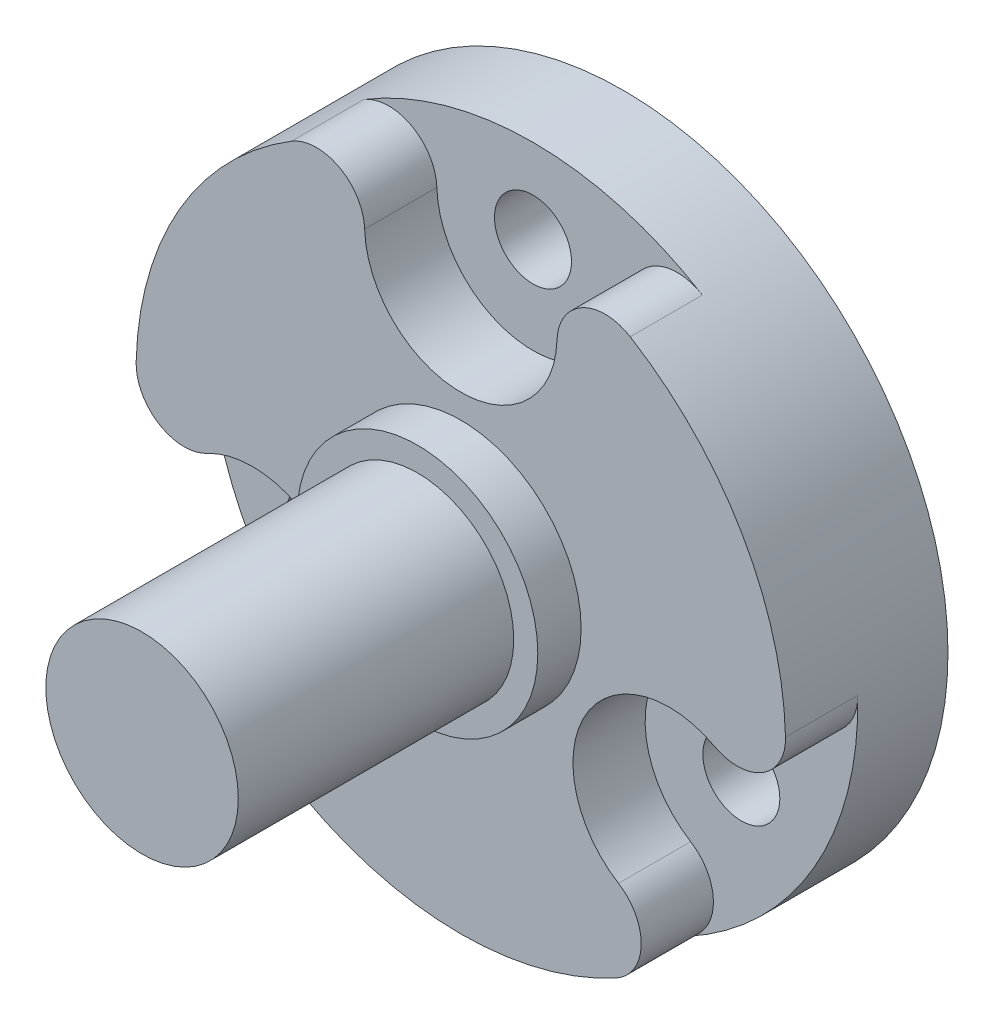
SolidWorks part; units mm, degrees
material "5052-H34"
ref_plane "正面" through (0, 0, 0) normal (0, 0, 1) x (1, 0, 0)
ref_plane "平面" through (0, 0, 0) normal (0, 1, 0) x (1, 0, 0)
ref_plane "右側面" through (0, 0, 0) normal (1, 0, 0) x (0, 0, -1)
sketch "ｽｹｯﾁ1" plane through (0, 0, 0) normal (0, 0, 1) x (1, 0, 0)
  circle A0 centre (0, 0) radius 13.5
  dimension "D1" = 27
extrude "ﾎﾞｽ - 押し出し1" add sketch "ｽｹｯﾁ1" along normal blind 20
sketch "ｽｹｯﾁ2" plane through (0, 0, 20) normal (0, 0, 1) x (1, 0, 0)
  line L0 (0, 0) -> (0, 10) construction
  circle A1 centre (0, 10) radius 1.6
  circle A2 centre (8.6603, -5) radius 1.6
  circle A3 centre (-8.6603, -5) radius 1.6
  circle A4 centre (0, 0) radius 10 construction
  dimension "D2" = 3.2
  dimension "D3" = 10
  dimension "D4" = 3
extrude "ｶｯﾄ - 押し出し1" cut sketch "ｽｹｯﾁ2" against normal through all
sketch "ｽｹｯﾁ3" plane through (0, 0, 20) normal (0, 0, 1) x (1, 0, 0)
  circle A0 centre (0, 0) radius 4
  circle A1 centre (0, 0) radius 13.5
  circle A2 centre (0, 0) radius 13.5
  dimension "D2" = 8
  dimension "D1" = 0
extrude "ｶｯﾄ - 押し出し4" cut sketch "ｽｹｯﾁ3" against normal blind 13.25
sketch "ｽｹｯﾁ4" plane through (0, 0, 6.75) normal (0, 0, 1) x (1, 0, 0)
  circle A0 centre (0, 0) radius 5
  circle A1 centre (0, 0) radius 4
  circle A2 centre (0, 0) radius 4
  dimension "D2" = 10
  dimension "D1" = 0
extrude "ﾎﾞｽ - 押し出し2" add sketch "ｽｹｯﾁ4" along normal blind 1.8
sketch "ｽｹｯﾁ5" plane through (0, 0, 6.75) normal (0, 0, 1) x (1, 0, 0)
  circle A0 centre (8.6603, -5) radius 1.6 construction
  circle A1 centre (-8.6603, -5) radius 1.6 construction
  circle A2 centre (0, 10) radius 1.6 construction
  circle A3 centre (8.6603, -5) radius 1.6
  circle A4 centre (-8.6603, -5) radius 1.6
  circle A5 centre (0, 10) radius 1.6
  circle A6 centre (0, 10) radius 4
  circle A7 centre (8.6603, -5) radius 4
  circle A8 centre (-8.6603, -5) radius 4
  dimension "D1" = 8
extrude "ｶｯﾄ - 押し出し6" cut sketch "ｽｹｯﾁ5" against normal blind 3
fillet "ﾌｨﾚｯﾄ1" radius 2 6 edges at (-12.6501, -4.7145, 5.25) (-10.4079, -8.598, 5.25) (10.4079, -8.598, 5.25) (12.6501, -4.7145, 5.25) (2.2422, 13.3125, 5.25) (-2.2422, 13.3125, 5.25)
